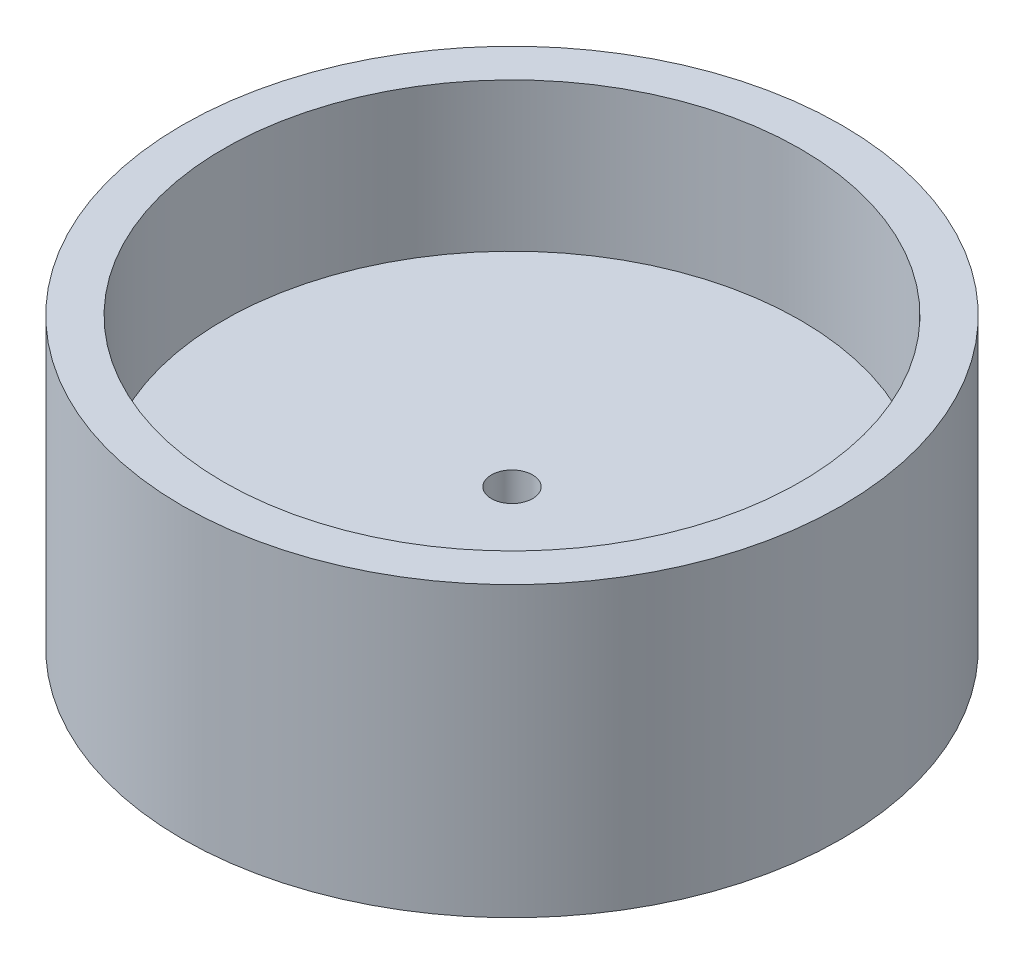
SolidWorks part; units mm, degrees
ref_plane "Plan de face" through (0, 0, 0) normal (0, 0, 1) x (1, 0, 0)
ref_plane "Plan de dessus" through (0, 0, 0) normal (0, 1, 0) x (1, 0, 0)
ref_plane "Plan de droite" through (0, 0, 0) normal (1, 0, 0) x (0, 0, -1)
sketch "Esquisse1" plane through (0, 0, 0) normal (0, 1, 0) x (1, 0, 0)
  circle A0 centre (0, 0) radius 40
extrude "Boss.-Extru.2" add sketch "Esquisse1" along normal blind 35
sketch "Esquisse4" plane through (0, 35, 0) normal (0, 1, 0) x (1, 0, 0)
  circle A0 centre (0, 0) radius 35
extrude "Enlèv. mat.-Extru.2" cut sketch "Esquisse4" against normal blind 18
sketch "Esquisse5" plane through (0, 0, 0) normal (0, -1, 0) x (-1, 0, 0)
  circle A0 centre (0, 0) radius 35
extrude "Enlèv. mat.-Extru.3" cut sketch "Esquisse5" against normal blind 12
sketch "Esquisse6" plane through (0, 17, 0) normal (0, 1, 0) x (1, 0, 0)
  circle A0 centre (0, 0) radius 2.5
extrude "Enlèv. mat.-Extru.4" cut sketch "Esquisse6" against normal blind 12
